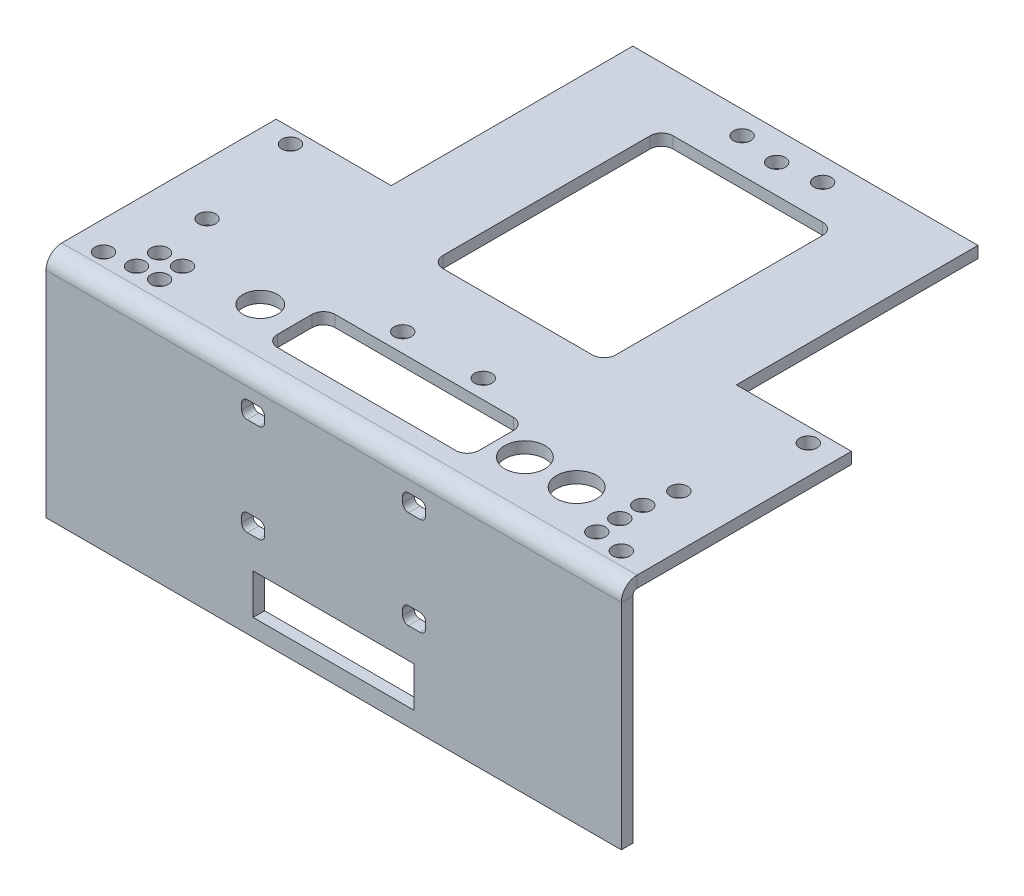
SolidWorks part; units mm, degrees
note: The reader was unsure of these and kept them because the rebuilt part matched: flange length of "Edge-Flange3".
ref_plane "Front Plane" through (0, 0, 0) normal (0, 0, 1) x (1, 0, 0)
ref_plane "Top Plane" through (0, 0, 0) normal (0, 1, 0) x (1, 0, 0)
ref_plane "Right Plane" through (0, 0, 0) normal (1, 0, 0) x (0, 0, -1)
sketch "Sketch2" plane through (0, 0, 0) normal (0, 1, 0) x (1, 0, 0)
  line L1 (0, 0) -> (100, 0)
  line L2 (0, 0) -> (0, 85)
  line L3 (0, 85) -> (100, 85)
  line L4 (100, 0) -> (100, 85)
  dimension "D1" = 85
  dimension "D2" = 100
base flange "Base-Flange1" sketch "Sketch2" thickness 2 reverse thickness direction no parameters "D1"=0.7366
sketch "Sketch15" plane through (0, 0, 0) normal (0, 1, 0) x (1, 0, 0)
  line L0 (50, 85) -> (50, 0) construction
  line L1 (0, 85) -> (20, 85)
  line L2 (0, 85) -> (0, 43)
  line L3 (0, 43) -> (20, 43)
  line L4 (20, 85) -> (20, 43)
  line L5 (100, 85) -> (0, 85) construction
  line L6 (0, 0) -> (100, 0) construction
  line L7 (0, 85) -> (0, 0) construction
  line L8 (100, 43) -> (80, 43)
  line L9 (80, 85) -> (80, 43)
  line L10 (100, 85) -> (80, 85)
  line L11 (100, 85) -> (100, 43)
  line L12 (100, 0) -> (100, 85) construction
  line L13 (0, 0) -> (100, 0)
  line L14 (0, 0) -> (0, 3)
  line L15 (0, 3) -> (100, 3)
  line L16 (100, 0) -> (100, 3)
  circle A0 centre (5, 8) radius 1.5
  circle A1 centre (5, 40.5) radius 1.5
  circle A2 centre (50, 80) radius 1.5
  circle A3 centre (95, 8) radius 1.5
  circle A4 centre (95, 40.5) radius 1.5
  dimension "D6" = 3
  dimension "D1" = 2.5
  dimension "D2" = 8
  dimension "D3" = 5
  dimension "D4" = 5
  dimension "D5" = 5
  dimension "D7" = 3
  dimension "D8" = 42
  dimension "D9" = 20
extrude "Cut-Extrude2" cut sketch "Sketch15" against normal blind 10 normal cut yes
edge flange "Edge-Flange3" sketch "Sketch21" flange angle 90 flange length 40 flange position material inside bend radius 0.7366 thickness 2 relief rectangular parameters "D6"=10
sketch "Sketch21" plane through (0, -2, -3) normal (0, 0, 1) x (-1, 0, 0)
  line L0 (0, 0) -> (-100, 0) construction
  line L1 (0, 0) -> (-100, 0)
  line L2 (-100, 0) -> (-100, 38)
  line L3 (-100, 38) -> (0, 38)
  line L4 (0, 38) -> (0, 0)
bend "EdgeBend3" bend radius 0.7366 bend angle 90 parameters "D5"=1
sketch "Sketch23" plane through (0, 0, -3) normal (0, 0, 1) x (1, 0, 0)
  line L0 (0, -40) -> (100, -40) construction
  line L1 (36, -40) -> (64, -40)
  line L2 (36, -40) -> (36, -30)
  line L3 (36, -30) -> (64, -30)
  line L4 (64, -40) -> (64, -30)
  line L6 (0, -2.7366) -> (0, -40) construction
  dimension "D1" = 10
  dimension "D2" = 36
  dimension "28" = 28
extrude "Cut-Extrude3" cut sketch "Sketch23" against normal blind 10 normal cut yes
sketch "Sketch24" plane through (0, 0, -3) normal (0, 0, 1) x (1, 0, 0)
  line L0 (64, -40) -> (64, -30) construction
  line L1 (36, -40) -> (64, -40)
  line L2 (36, -40) -> (36, -37)
  line L3 (36, -37) -> (64, -37)
  line L4 (64, -40) -> (64, -37)
  dimension "D1" = 3
base flange "Tab1" sketch "Sketch24" thickness 2 reverse thickness direction no parameters "D1"=0.7366
sketch "Sketch25" plane through (0, 0, 0) normal (0, 1, 0) x (1, 0, 0)
  line L0 (80, 85) -> (20, 85) construction
  line L1 (50, 85) -> (50, 81.5) construction
  line L3 (37, 75) -> (63, 75)
  line L4 (35, 73) -> (35, 37)
  line L5 (37, 35) -> (63, 35)
  line L6 (65, 73) -> (65, 37)
  circle A0 centre (43, 81) radius 1.5
  circle A4 centre (50, 80) radius 1.5 construction
  circle A5 centre (43, 22) radius 1.5
  circle A8 centre (9, 22) radius 1.5
  circle A9 centre (91, 22) radius 1.5
  circle A10 centre (57, 22) radius 1.5
  circle A11 centre (57, 81) radius 1.5
  arc A12 (35, 37) -> (37, 35) centre (37, 37) ccw
  arc A13 (63, 35) -> (65, 37) centre (63, 37) ccw
  arc A14 (63, 75) -> (65, 73) centre (63, 73) cw
  arc A15 (37, 75) -> (35, 73) centre (37, 73) ccw
  point P24 (35, 35)
  point P29 (65, 75)
  point P32 (35, 75)
  dimension "D2" = 3
  dimension "D5" = 30
  dimension "D10" = 2
  dimension "D1" = 4
  dimension "D3" = 7
  dimension "D4" = 59
  dimension "D6" = 34
  dimension "D7" = 40
  dimension "D8" = 10
  dimension "D9" = 15
extrude "Cut-Extrude11" cut sketch "Sketch25" against normal blind 10 normal cut yes
sketch "Sketch28" plane through (0, 0, 0) normal (0, 1, 0) x (1, 0, 0)
  line L1 (34.5, 8.7366) -> (65.5, 8.7366)
  line L2 (32.5, 10.7366) -> (32.5, 16.7366)
  line L3 (34.5, 18.7366) -> (65.5, 18.7366)
  line L4 (67.5, 10.7366) -> (67.5, 16.7366)
  line L5 (0, 5.7366) -> (100, 5.7366) construction
  line L6 (0, 43) -> (0, 5.7366) construction
  arc A0 (65.5, 18.7366) -> (67.5, 16.7366) centre (65.5, 16.7366) cw
  arc A1 (65.5, 8.7366) -> (67.5, 10.7366) centre (65.5, 10.7366) ccw
  arc A2 (34.5, 8.7366) -> (32.5, 10.7366) centre (34.5, 10.7366) cw
  arc A3 (32.5, 16.7366) -> (34.5, 18.7366) centre (34.5, 16.7366) cw
  point P12 (67.5, 8.7366)
  point P15 (32.5, 8.7366)
  point P18 (32.5, 18.7366)
  dimension "D5" = 2
  dimension "D1" = 35
  dimension "D2" = 10
  dimension "D3" = 3
  dimension "D4" = 32.5
extrude "Cut-Extrude7" cut sketch "Sketch28" against normal blind 10 normal cut yes
sketch "Sketch33" plane through (0, 0, -3) normal (0, 0, 1) x (1, 0, 0)
  line L0 (0, -2.7366) -> (100, -2.7366) construction
  line L5 (35, -4.7366) -> (37, -4.7366)
  line L6 (34, -5.7366) -> (34, -6.7366)
  line L7 (35, -7.7366) -> (37, -7.7366)
  line L8 (38, -5.7366) -> (38, -6.7366)
  line L9 (35, -21.7366) -> (37, -21.7366)
  line L10 (34, -22.7366) -> (34, -23.7366)
  line L11 (35, -24.7366) -> (37, -24.7366)
  line L12 (38, -22.7366) -> (38, -23.7366)
  line L21 (50, -2.7366) -> (50, -30) construction
  line L22 (64, -30) -> (36, -30) construction
  line L23 (65, -24.7366) -> (63, -24.7366)
  line L24 (62, -22.7366) -> (62, -23.7366)
  line L25 (65, -21.7366) -> (63, -21.7366)
  line L26 (66, -22.7366) -> (66, -23.7366)
  line L27 (65, -7.7366) -> (63, -7.7366)
  line L28 (62, -5.7366) -> (62, -6.7366)
  line L29 (65, -4.7366) -> (63, -4.7366)
  line L30 (66, -5.7366) -> (66, -6.7366)
  arc A1 (34, -23.7366) -> (35, -24.7366) centre (35, -23.7366) ccw
  arc A2 (37, -24.7366) -> (38, -23.7366) centre (37, -23.7366) ccw
  arc A3 (38, -22.7366) -> (37, -21.7366) centre (37, -22.7366) ccw
  arc A4 (35, -21.7366) -> (34, -22.7366) centre (35, -22.7366) ccw
  arc A5 (35, -4.7366) -> (34, -5.7366) centre (35, -5.7366) ccw
  arc A6 (34, -6.7366) -> (35, -7.7366) centre (35, -6.7366) ccw
  arc A7 (37, -7.7366) -> (38, -6.7366) centre (37, -6.7366) ccw
  arc A8 (37, -4.7366) -> (38, -5.7366) centre (37, -5.7366) cw
  arc A9 (63, -24.7366) -> (62, -23.7366) centre (63, -23.7366) cw
  arc A10 (62, -22.7366) -> (63, -21.7366) centre (63, -22.7366) cw
  arc A11 (66, -23.7366) -> (65, -24.7366) centre (65, -23.7366) cw
  arc A12 (65, -21.7366) -> (66, -22.7366) centre (65, -22.7366) cw
  arc A13 (63, -7.7366) -> (62, -6.7366) centre (63, -6.7366) cw
  arc A14 (63, -4.7366) -> (62, -5.7366) centre (63, -5.7366) ccw
  arc A15 (65, -4.7366) -> (66, -5.7366) centre (65, -5.7366) cw
  arc A16 (66, -6.7366) -> (65, -7.7366) centre (65, -6.7366) cw
  point P14 (34, -24.7366)
  point P19 (38, -24.7366)
  point P24 (34, -21.7366)
  point P27 (34, -4.7366)
  point P30 (34, -7.7366)
  point P35 (38, -4.7366)
  dimension "D8" = 1
  dimension "D1" = 4
  dimension "D2" = 3
  dimension "D3" = 2
  dimension "D4" = 14
  dimension "D5" = 3
  dimension "D6" = 4
  dimension "D7" = 12
  dimension "D9" = 12
extrude "Cut-Extrude9" cut sketch "Sketch33" against normal blind 10 normal cut yes
sketch "Sketch34" plane through (0, 0, 0) normal (0, 1, 0) x (1, 0, 0)
  line L0 (0, 5.7366) -> (100, 5.7366) construction
  line L1 (0, 43) -> (0, 5.7366) construction
  line L2 (100, 5.7366) -> (100, 43) construction
  circle A0 centre (10, 8.7366) radius 1.5
  circle A1 centre (90, 8.7366) radius 1.5
  circle A2 centre (14, 8.7366) radius 1.5
  circle A4 centre (14, 12.7366) radius 1.5
  circle A5 centre (10, 12.7366) radius 1.5
  circle A6 centre (90, 12.7366) radius 1.5
  circle A7 centre (90, 16.7366) radius 1.5
  dimension "D2" = 3
  dimension "D6" = 3
  dimension "D7" = 3
  dimension "D10" = 3
  dimension "D1" = 3
  dimension "D3" = 10
  dimension "D4" = 10
  dimension "D5" = 3
  dimension "D8" = 4
  dimension "D9" = 2
extrude "Cut-Extrude10" cut sketch "Sketch34" against normal blind 10 normal cut yes
sketch "Sketch35" plane through (0, 0, 0) normal (0, 1, 0) x (1, 0, 0)
  line L0 (32.5, 16.7366) -> (32.5, 10.7366) construction
  line L1 (34.5, 8.7366) -> (65.5, 8.7366) construction
  line L2 (67.5, 10.7366) -> (67.5, 16.7366) construction
  circle A0 centre (26.5, 13.7366) radius 3
  circle A1 centre (72.5, 13.7366) radius 3.5
  circle A3 centre (81.5, 13.7366) radius 3.5
  dimension "D1" = 6
  dimension "D4" = 7
  dimension "D7" = 2
  dimension "D2" = 6
  dimension "D3" = 5
  dimension "D5" = 5
  dimension "D6" = 5
extrude "Cut-Extrude12" cut sketch "Sketch35" against normal blind 10 normal cut yes
sketch "Bend-Lines1" [suppressed] plane through (0, 0, 0) normal (0, 1, 0) x (1, 0, 0)
sketch "Bounding-Box1" [suppressed] plane through (0, 0, 0) normal (0, 1, 0) x (1, 0, 0)
sheet metal parameters "Sheet-Metal1" thickness 2 parameters "D1"=0.7366
flat pattern "Flat-Pattern1" [suppressed]
sketch "Bend-Lines2" plane through (0, 0, 0) normal (0, 1, 0) x (1, 0, 0)
sketch3d "Bounding-Box2" [suppressed]
  line L0 (100, 85, 0) -> (0, 85, 0) construction
  line L1 (100, 0, 0) -> (0, 0, 0) construction
  line L2 (100, 85, 0) -> (100, 0, 0) construction
  line L3 (0, 85, 0) -> (0, 0, 0) construction
sheet metal parameters "Sheet-Metal4" thickness 2 parameters "D1"=0.7366
flat pattern "Flat-Pattern1"
sketch "Bend-Lines2" plane through (0, 0, 0) normal (0, 1, 0) x (1, 0, 0)
sketch3d "Bounding-Box2" [suppressed]
  line L0 (100, 85, 0) -> (0, 85, 0) construction
  line L1 (100, 3, 0) -> (0, 3, 0) construction
  line L2 (100, 85, 0) -> (100, 3, 0) construction
  line L3 (0, 85, 0) -> (0, 3, 0) construction
sheet metal parameters "Sheet-Metal6" thickness 2 parameters "D1"=0.7366
flat pattern "Flat-Pattern1"
sketch "Bend-Lines2" plane through (0, 0, 0) normal (0, 1, 0) x (1, 0, 0)
  line L0 (0, 4.3727) -> (100, 4.3727) construction
  line L1 (0, 4.3727) -> (100, 4.3727) construction
sketch3d "Bounding-Box2" [suppressed]
  line L0 (0, -24.2546, 0) -> (0, 85, 0) construction
  line L1 (100, -24.2546, 0) -> (100, 85, 0) construction
  line L2 (0, -24.2546, 0) -> (100, -24.2546, 0) construction
  line L3 (0, 85, 0) -> (100, 85, 0) construction
bend of the flat pattern "Flatten-<EdgeBend3>1"
sheet metal parameters "Sheet-Metal7" thickness 2 parameters "D1"=0.7366
flat pattern "Flat-Pattern1"
sketch "Bend-Lines2" plane through (0, 0, 0) normal (0, 1, 0) x (1, 0, 0)
  line L0 (0, 4.3727) -> (100, 4.3727) construction
  line L1 (0, 4.3727) -> (100, 4.3727) construction
sketch3d "Bounding-Box2" [suppressed]
  line L0 (0, -24.2546, 0) -> (0, 85, 0) construction
  line L1 (100, -24.2546, 0) -> (100, 85, 0) construction
  line L2 (0, -24.2546, 0) -> (100, -24.2546, 0) construction
  line L3 (0, 85, 0) -> (100, 85, 0) construction
bend of the flat pattern "Flatten-<EdgeBend3>1"
sheet metal parameters "Sheet-Metal8" thickness 2 parameters "D1"=0.7366
flat pattern "Flat-Pattern8"
sketch "Bend-Lines3" plane through (0, 0, 0) normal (0, 1, 0) x (1, 0, 0)
  line L0 (0, 4.3727) -> (100, 4.3727) construction
  line L1 (0, 4.3727) -> (100, 4.3727) construction
sketch3d "Bounding-Box3" [suppressed]
  line L0 (0, -24.2546, 0) -> (0, 85, 0) construction
  line L1 (100, -24.2546, 0) -> (100, 85, 0) construction
  line L2 (0, -24.2546, 0) -> (100, -24.2546, 0) construction
  line L3 (0, 85, 0) -> (100, 85, 0) construction
bend of the flat pattern "Flatten-<EdgeBend3>2"
sheet metal parameters "Sheet-Metal12" thickness 2 parameters "D1"=0.7366
flat pattern "Flat-Pattern8"
sketch "Bend-Lines3" plane through (0, 0, 0) normal (0, 1, 0) x (1, 0, 0)
  line L0 (0, 4.3727) -> (100, 4.3727) construction
  line L1 (0, 4.3727) -> (100, 4.3727) construction
sketch3d "Bounding-Box3" [suppressed]
  line L0 (0, -34.2546, 0) -> (0, 85, 0) construction
  line L1 (100, -34.2546, 0) -> (100, 85, 0) construction
  line L2 (0, -34.2546, 0) -> (100, -34.2546, 0) construction
  line L3 (0, 85, 0) -> (100, 85, 0) construction
bend of the flat pattern "Flatten-<EdgeBend3>2"
sheet metal parameters "Sheet-Metal15" thickness 2 parameters "D1"=0.7366
flat pattern "Flat-Pattern8"
sketch "Bend-Lines3" plane through (0, 0, 0) normal (0, 1, 0) x (1, 0, 0)
  line L0 (0, 4.3727) -> (100, 4.3727) construction
  line L1 (0, 4.3727) -> (100, 4.3727) construction
sketch3d "Bounding-Box3" [suppressed]
  line L0 (0, -34.2546, 0) -> (0, 85, 0) construction
  line L1 (100, -34.2546, 0) -> (100, 85, 0) construction
  line L2 (0, -34.2546, 0) -> (100, -34.2546, 0) construction
  line L3 (0, 85, 0) -> (100, 85, 0) construction
bend of the flat pattern "Flatten-<EdgeBend3>2"
sheet metal parameters "Sheet-Metal16" thickness 2 parameters "D1"=0.7366
flat pattern "Flat-Pattern8"
sketch "Bend-Lines3" plane through (0, 0, 0) normal (0, 1, 0) x (1, 0, 0)
  line L0 (0, 4.3727) -> (100, 4.3727) construction
  line L1 (0, 4.3727) -> (100, 4.3727) construction
sketch3d "Bounding-Box3" [suppressed]
  line L0 (0, -34.2546, 0) -> (0, 85, 0) construction
  line L1 (100, -34.2546, 0) -> (100, 85, 0) construction
  line L2 (0, -34.2546, 0) -> (100, -34.2546, 0) construction
  line L3 (0, 85, 0) -> (100, 85, 0) construction
bend of the flat pattern "Flatten-<EdgeBend3>2"
sheet metal parameters "Sheet-Metal17" thickness 2 parameters "D1"=0.7366
flat pattern "Flat-Pattern8"
sketch "Bend-Lines3" plane through (0, 0, 0) normal (0, 1, 0) x (1, 0, 0)
  line L0 (0, 4.3727) -> (100, 4.3727) construction
  line L1 (0, 4.3727) -> (100, 4.3727) construction
sketch3d "Bounding-Box3" [suppressed]
  line L0 (0, -24.2546, 0) -> (0, 85, 0) construction
  line L1 (100, -24.2546, 0) -> (100, 85, 0) construction
  line L2 (0, -24.2546, 0) -> (100, -24.2546, 0) construction
  line L3 (0, 85, 0) -> (100, 85, 0) construction
bend of the flat pattern "Flatten-<EdgeBend3>2"
sheet metal parameters "Sheet-Metal18" thickness 2 parameters "D1"=0.7366
flat pattern "Flat-Pattern8"
sketch "Bend-Lines3" plane through (0, 0, 0) normal (0, 1, 0) x (1, 0, 0)
  line L0 (0, 4.3727) -> (100, 4.3727) construction
  line L1 (0, 4.3727) -> (100, 4.3727) construction
sketch3d "Bounding-Box3" [suppressed]
  line L0 (0, -34.2546, 0) -> (0, 85, 0) construction
  line L1 (100, -34.2546, 0) -> (100, 85, 0) construction
  line L2 (0, -34.2546, 0) -> (100, -34.2546, 0) construction
  line L3 (0, 85, 0) -> (100, 85, 0) construction
bend of the flat pattern "Flatten-<EdgeBend3>2"
